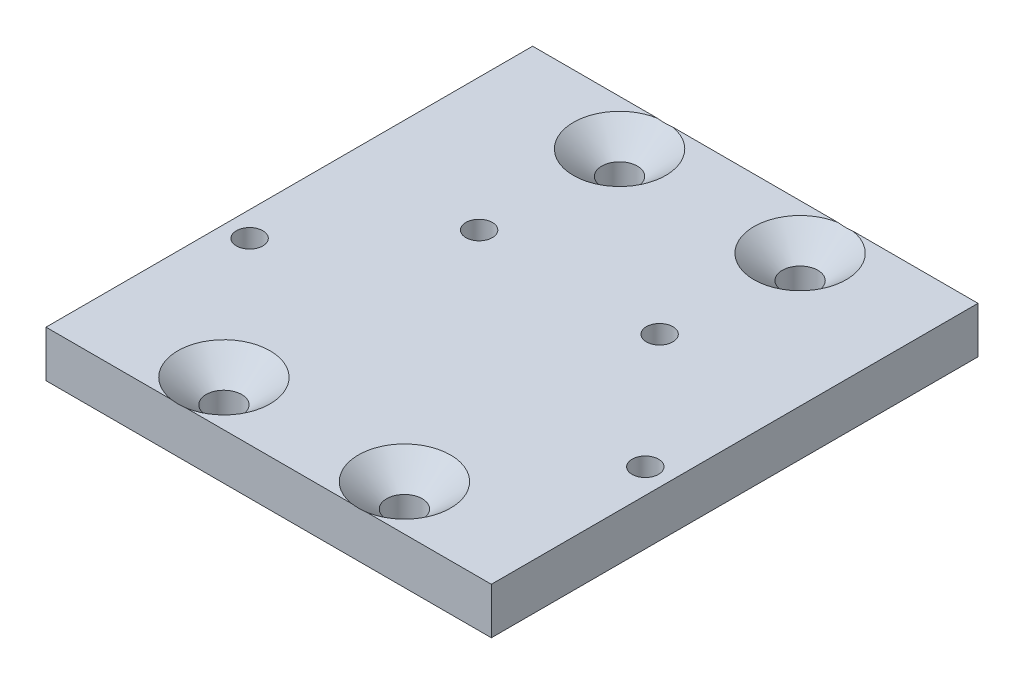
SolidWorks part; units mm, degrees
ref_plane "Front" through (0, 0, 0) normal (0, 0, 1) x (1, 0, 0)
ref_plane "Top" through (0, 0, 0) normal (0, 1, 0) x (1, 0, 0)
ref_plane "Right" through (0, 0, 0) normal (1, 0, 0) x (0, 0, -1)
sketch "Sketch1" plane through (0, -2000, 0) normal (0, 1, 0) x (1, 0, 0)
  line L0 (-1528.0866, 2973.3423) -> (-1573.8325, 2973.3423) construction
  line L1 (-1573.8325, 2973.3423) -> (-1528.0866, 2973.3423)
  line L2 (-1573.8325, 2973.3423) -> (-1573.8325, 2923.3551)
  line L3 (-1573.8325, 2923.3551) -> (-1528.0866, 2923.3551)
  line L4 (-1528.0866, 2973.3423) -> (-1528.0866, 2923.3551)
  circle A0 centre (-1560.2306, 2968.6687) radius 1.905 construction
  circle A1 centre (-1541.6886, 2968.6687) radius 1.905 construction
  circle A2 centre (-1541.6886, 2928.0287) radius 1.905 construction
  circle A3 centre (-1560.2306, 2928.0287) radius 1.905 construction
  point P20 (-1560.2306, 2928.0287)
  point P21 (-1541.6886, 2928.0287)
  point P22 (-1541.6886, 2968.6687)
  point P23 (-1560.2306, 2968.6687)
  dimension "D1" = 45.7458
  dimension "D2" = 49.9872
  dimension "D3" = 4.6736
  dimension "D4" = 45.3136
  dimension "D5" = 13.6019
  dimension "D6" = 32.1439
extrude "Boss-Extrude1" add sketch "Sketch1" along normal blind 4.7625
sketch "Sketch5" plane through (0, -1995.2375, 0) normal (0, 1, 0) x (1, 0, 0)
  point P0 (-1560.2306, 2928.0287)
  point P1 (-1560.2306, 2968.6687)
  point P3 (-1541.6886, 2968.6687)
  point P5 (-1541.6886, 2928.0287)
hole_wizard "CSK for #6 Flat Head Machine Screw (100)8" positions "3DSketch4" profile "Sketch7" countersink size "#6" standard "ANSI Inch" end condition through all
sketch3d "3DSketch4"
  point P0 (-1560.2306, -1995.2375, -2968.6687)
  point P4 (-1560.2306, -1995.2375, -2928.0287)
  point P7 (-1541.6886, -1995.2375, -2928.0287)
  point P10 (-1541.6886, -1995.2375, -2968.6687)
sketch "Sketch7" plane through (-1560.2306, -1995.2375, -2968.6687) normal (1, 0, 0) x (0, 0, 1)
  line L0 (0, 0) -> (0, 4.7625)
  line L1 (0, 4.7625) -> (1.8288, 4.7625)
  line L2 (1.8288, 4.7625) -> (1.8288, 2.4386)
  line L3 (1.8288, 2.4386) -> (4.7351, 0)
  line L5 (4.7351, 0) -> (0, 0)
  line L6 (-1.8288, 2.4386) -> (-4.7351, 0) construction
  line L11 (0, -6.35) -> (0, 107.95) construction
  dimension "Thru Hole Dia." = 3.6576
  dimension "Thru Hole Depth" = 4.7625
  dimension "Near C'Sink Dia." = 9.4701
  dimension "Near C'Sink Angle" = 100
ref_plane "Plane1" through (-1550.9596, 0, 0) normal (1, 0, 0) x (0, 0, -1)
ref_plane "Plane2" through (0, 0, -2948.3487) normal (0, 0, -1) x (-1, 0, 0)
ref_axis "axis" through (-1550.9596, -2000.2381, -2948.3487) along (0, 1, 0)
sketch "Sketch8" plane through (0, -2000, 0) normal (0, -1, 0) x (1, 0, 0)
  line L0 (-1540.9282, -2923.3551) -> (-1528.0866, -2923.3551) construction
  line L1 (-1528.0866, -2923.3551) -> (-1528.0866, -2973.3423) construction
  circle A0 centre (-1541.6843, -2954.2369) radius 1.3589
  circle A1 centre (-1560.2263, -2954.2369) radius 1.3589
  circle A2 centre (-1571.2772, -2941.7147) radius 1.3589
  circle A3 centre (-1530.6333, -2941.7147) radius 1.3589
  dimension "D1" = 18.3596
  dimension "D2" = 30.8818
  dimension "D3" = 2.5467
  dimension "D4" = 13.5976
  dimension "D5" = 32.1396
  dimension "D6" = 43.1905
extrude "Cut-Extrude1" cut sketch "Sketch8" against normal through all
